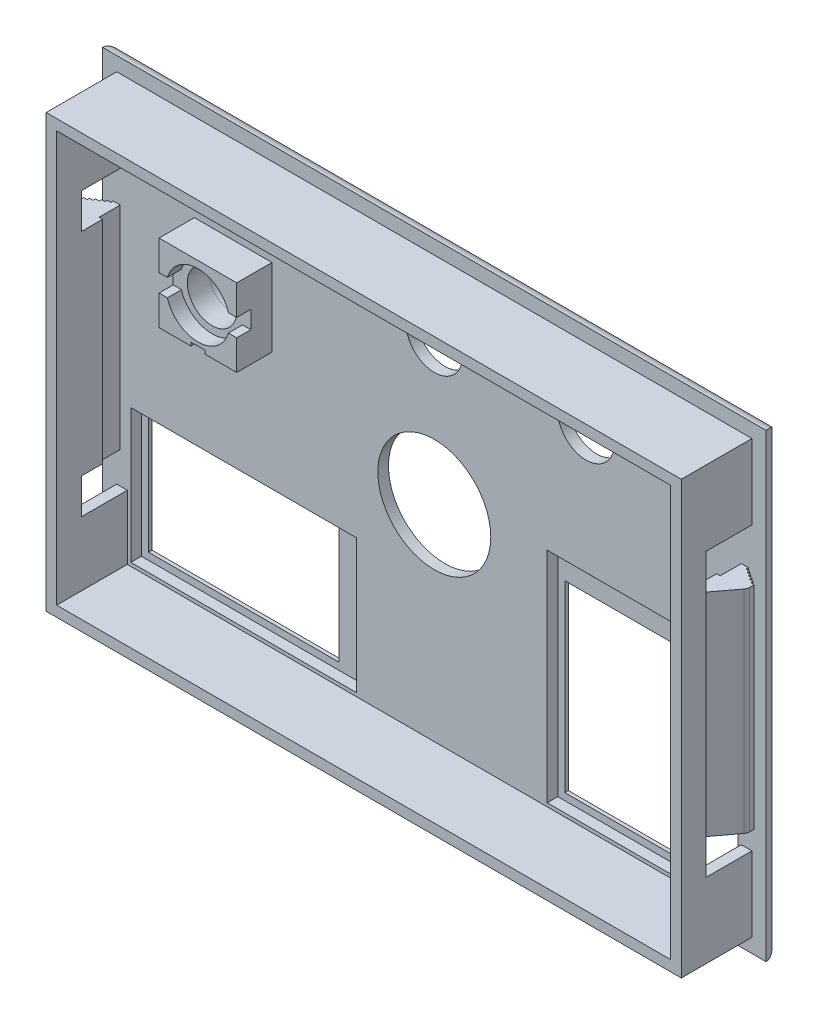
SolidWorks part; units mm, degrees
ref_plane "前视基准面" through (0, 0, 0) normal (0, 0, 1) x (1, 0, 0)
ref_plane "上视基准面" through (0, 0, 0) normal (0, 1, 0) x (1, 0, 0)
ref_plane "右视基准面" through (0, 0, 0) normal (1, 0, 0) x (0, 0, -1)
sketch "草图1" plane through (0, 0, 0) normal (0, 0, 1) x (1, 0, 0)
  line L1 (-47, 32.6) -> (47, 32.6)
  line L2 (-47, 32.6) -> (-47, -32.6)
  line L3 (-47, -32.6) -> (47, -32.6)
  line L4 (47, 32.6) -> (47, -32.6)
  line L5 (-47, 32.6) -> (47, -32.6) construction
  line L6 (-47, -32.6) -> (47, 32.6) construction
  point P0 (0, 0)
  dimension "D1" = 94
  dimension "D2" = 65.2
extrude "凸台-拉伸1" add sketch "草图1" along normal blind 2 contours L3 L4 L1 L2
sketch "草图2" plane through (0, 0, 2) normal (0, 0, 1) x (1, 0, 0)
  line L0 (-15, -27.6) -> (-42, -10.6) construction
  line L1 (-15, -27.6) -> (-42, -27.6)
  line L2 (-15, -27.6) -> (-15, -10.6)
  line L3 (-15, -10.6) -> (-42, -10.6)
  line L4 (-42, -27.6) -> (-42, -10.6)
  line L5 (42, -27.6) -> (17, -27.6)
  line L6 (42, -27.6) -> (42, -1.6)
  line L7 (42, -1.6) -> (17, -1.6)
  line L8 (17, -27.6) -> (17, -1.6)
  line L9 (-15, -10.6) -> (-42, -27.6) construction
  line L10 (42, -27.6) -> (17, -1.6) construction
  line L11 (42, -1.6) -> (17, -27.6) construction
  circle A0 centre (0, 0) radius 8
  circle A1 centre (-28.5, 12.7) radius 3.5
  circle A2 centre (37.5, 20.2) radius 4
  circle A3 centre (21.5, 20.2) radius 4
  circle A4 centre (0, 20.2) radius 4
  point P14 (-28.5, -19.1)
  point P24 (29.5, -14.6)
  dimension "D5" = 16
  dimension "D6" = 7
  dimension "D8" = 8
  dimension "D11" = 8
  dimension "D15" = 8
  dimension "D16" = 8
  dimension "D1" = 17
  dimension "D2" = 27
  dimension "D3" = 26
  dimension "D4" = 25
  dimension "D7" = 19.1
  dimension "D9" = 28.5
  dimension "D10" = 29.5
  dimension "D12" = 20.2
  dimension "D13" = 8
  dimension "D17" = 12.7
extrude "切除-拉伸1" cut sketch "草图2" against normal blind 2
sketch "草图3" plane through (0, 0, 2) normal (0, 0, 1) x (1, 0, 0)
  line L1 (43, -28.6) -> (-43, -28.6)
  line L2 (43, -28.6) -> (43, 28.6)
  line L3 (43, 28.6) -> (-43, 28.6)
  line L4 (-43, -28.6) -> (-43, 28.6)
  line L5 (45, -30.6) -> (-45, -30.6)
  line L6 (45, -30.6) -> (45, 30.6)
  line L7 (45, 30.6) -> (-45, 30.6)
  line L8 (-45, -30.6) -> (-45, 30.6)
  dimension "D1" = 2
  dimension "D2" = 2
  dimension "D3" = 2
  dimension "D4" = 2
  dimension "D5" = 43
  dimension "D6" = 28.6
  dimension "D7" = 28.6
  dimension "D8" = 43
extrude "凸台-拉伸2" add sketch "草图3" along normal blind 10 contours L6 L7 L8 L5 | L2 L3 L4 L1
sketch "草图4" plane through (0, 0, 0) normal (0, 0, -1) x (-1, 0, 0)
  circle A1 centre (0, 0) radius 9
  circle A2 centre (0, 20.2) radius 5
  circle A3 centre (-21.5, 20.2) radius 5
  circle A4 centre (-37.5, 20.2) radius 5
  dimension "D2" = 18
  dimension "D11" = 10
  dimension "D12" = 10
  dimension "D13" = 10
extrude "切除-拉伸4" cut sketch "草图4" against normal blind 0.5
sketch "草图5" plane through (0, 0, 2) normal (0, 0, 1) x (1, 0, 0)
  line L0 (17, -27.6) -> (42, -27.6) construction
  line L1 (43, -28.6) -> (16, -28.6)
  line L2 (43, -28.6) -> (43, 2.4)
  line L3 (43, 2.4) -> (16, 2.4)
  line L4 (16, -28.6) -> (16, 2.4)
  line L5 (42, -27.6) -> (42, -1.6) construction
  line L6 (17, -1.6) -> (17, -27.6) construction
  line L7 (42, -1.6) -> (17, -1.6) construction
  line L8 (-42, -27.6) -> (-15, -27.6) construction
  line L9 (-11, -28.6) -> (-43, -28.6)
  line L10 (-11, -28.6) -> (-11, -9.6)
  line L11 (-11, -9.6) -> (-43, -9.6)
  line L12 (-43, -28.6) -> (-43, -9.6)
  line L14 (-42, -10.6) -> (-42, -27.6) construction
  line L15 (-15, -10.6) -> (-42, -10.6) construction
  line L16 (-15, -27.6) -> (-15, -10.6) construction
  dimension "D1" = 1
  dimension "D2" = 1
  dimension "D3" = 1
  dimension "D4" = 4
  dimension "D5" = 1
  dimension "D6" = 1
  dimension "D7" = 1
  dimension "D8" = 4
extrude "切除-拉伸5" cut sketch "草图5" against normal blind 1.5
sketch "草图6" plane through (0, 0, 2) normal (0, 0, 1) x (1, 0, 0)
  line L0 (-28.5, 9.2) -> (-28.5, 16.2) construction
  line L6 (-22.5, 6.7) -> (-34.5, 6.7)
  line L7 (-22.5, 6.7) -> (-22.5, 18.7)
  line L8 (-22.5, 18.7) -> (-34.5, 18.7)
  line L9 (-34.5, 6.7) -> (-34.5, 18.7)
  line L10 (-22.5, 6.7) -> (-34.5, 18.7) construction
  line L11 (-22.5, 18.7) -> (-34.5, 6.7) construction
  circle A0 centre (-28.5, 12.7) radius 3.5 construction
  point P0 (-28.5, 12.7)
  circle M18 centre (-28.5, 12.7) radius 3.5
  dimension "D1" = 12
  dimension "D2" = 12
extrude "凸台-拉伸4" add sketch "草图6" along normal blind 5 separate body contours L9 L6 L7 L8 M18
sketch "草图7" plane through (0, 0, 7) normal (0, 0, 1) x (1, 0, 0)
  line L0 (-28.5, 9.2) -> (-28.5, 4.2907) construction
  line L1 (-22.5, 6.7) -> (-34.5, 6.7) construction
  line L2 (-27.5, 6.7) -> (-29.5, 6.7)
  line L3 (-27.5, 6.7) -> (-27.5, 7.7)
  line L4 (-27.5, 7.7) -> (-29.5, 7.7)
  line L5 (-29.5, 6.7) -> (-29.5, 7.7)
  circle A0 centre (-28.5, 12.7) radius 3.5 construction
  dimension "D1" = 2
  dimension "D3" = 1
extrude "切除-拉伸6" cut sketch "草图7" against normal blind 3
sketch "草图9" plane through (45, 0, 0) normal (1, 0, 0) x (0, 0, -1)
  line L0 (-8.5, 20) -> (-8.5, 15)
  line L1 (-8.5, 15) -> (-2.5, 15)
  line L2 (-2.5, 15) -> (-2.5, -15)
  line L3 (-2.5, -15) -> (-8.5, -15)
  line L4 (-8.5, -15) -> (-8.5, -20)
  line L5 (-8.5, -20) -> (-4.5187, -20)
  line L6 (-4.5187, -20) -> (-2, -20)
  line L7 (-2, -20) -> (-2, 20)
  line L8 (-2, 20) -> (-8.5, 20)
  line L9 (-2, -30.6) -> (-2, 30.6) construction
  line L10 (-20.086, 0) -> (-0.5045, 0) construction
  point P13 (-8.5, -17.5)
  point P14 (-8.5, 17.5)
  dimension "D1" = 30
  dimension "D2" = 40
  dimension "D4" = 0.5
  dimension "D5" = 6
  dimension "D6" = 6
extrude "切除-拉伸7" cut sketch "草图9" against normal up to next (2 mm away)
sketch "草图10" plane through (45, 0, 0) normal (1, 0, 0) x (0, 0, -1)
  line L1 (-8.5, 15) -> (-2.5, 15)
  line L2 (-8.5, 15) -> (-8.5, -15)
  line L3 (-8.5, -15) -> (-2.5, -15)
  line L4 (-2.5, 15) -> (-2.5, -15)
extrude "凸台-拉伸5" add sketch "草图10" along normal blind 3
sketch "草图13" plane through (0, 15, 0) normal (0, 1, 0) x (1, 0, 0)
  line L1 (48, -2.5) -> (48, -8.5) construction
  line L2 (48, -4.5) -> (48, -2.5)
  line L3 (43, -2.5) -> (48, -2.5) construction
  line L6 (48, -4.5) -> (47.5, -4.5)
  line L7 (47.5, -4.5) -> (47.5, -4.1693)
  line L8 (47.5, -4.1693) -> (47, -4.1693)
  line L9 (47, -4.1693) -> (47, -3.84)
  line L10 (47, -3.84) -> (46.5, -3.84)
  line L11 (46.5, -3.84) -> (46.5, -3.503)
  line L12 (46.5, -3.503) -> (46, -3.503)
  line L13 (46, -3.503) -> (46, -3.1684)
  line L14 (46, -3.1684) -> (45.5, -3.1684)
  line L15 (45.5, -3.1684) -> (45.5, -2.8377)
  line L16 (45.5, -2.8377) -> (45, -2.8377)
  line L17 (45, -2.8377) -> (45, -2.5)
  line L18 (48, -2.5) -> (45, -2.5)
  point P19 (47.25, -4.1693)
  dimension "D1" = 0.5
  dimension "D2" = 0.5
  dimension "D3" = 0.5
  dimension "D4" = 0.5
  dimension "D5" = 0.5
  dimension "D6" = 0.5
  dimension "D7" = 2
  dimension "D8" = 1.6693
  dimension "D9" = 1.34
  dimension "D10" = 1.003
  dimension "D11" = 0.6684
  dimension "D12" = 0.3377
extrude "切除-拉伸9" cut sketch "草图13" against normal up to next (30 mm away)
sketch "草图14" plane through (0, 15, 0) normal (0, 1, 0) x (1, 0, 0)
  line L0 (45, -8.5) -> (48, -4.5)
  line L1 (48, -4.5) -> (48, -8.5)
  line L2 (48, -8.5) -> (45, -8.5)
extrude "切除-拉伸10" cut sketch "草图14" against normal up to next (30 mm away)
sketch "草图15" plane through (0, 15, 0) normal (0, 1, 0) x (1, 0, 0)
  line L0 (47.5, -4.5) -> (47.5, -5.1667)
  line L1 (48, -4.5) -> (45, -8.5) construction
  line L2 (47.5, -5.1667) -> (48, -4.5)
  line L3 (48, -4.5) -> (47.5, -4.5)
extrude "切除-拉伸11" cut sketch "草图15" against normal up to next (30 mm away)
fillet "圆角1" radius 1 1 edges at (47.5, 0, 5.1667)
ref_plane "基准面1" through (0, 0, 0) normal (0, -1, 0) x (-1, 0, 0)
ref_plane "基准面2" through (0, 0, 0) normal (1, 0, 0) x (0, 0, -1)
fillet "圆角2" radius 2 4 edges at (47, 0, 0) (0, -32.6, 0) (-47, 0, 0) (0, 32.6, 0)
mirror "镜向9" about plane through (0, 0, 0) normal (1, 0, 0) of "凸台-拉伸5", "切除-拉伸9", "切除-拉伸11", "切除-拉伸10", "圆角1", "切除-拉伸7"
sketch "草图17" plane through (0, 0, 7) normal (0, 0, 1) x (1, 0, 0)
  circle A0 centre (-28.5, 12.7) radius 4.5
  circle A1 centre (-28.5, 12.7) radius 3.5 construction
  dimension "D1" = 9
extrude "切除-拉伸13" cut sketch "草图17" against normal blind 2
sketch "草图18" plane through (0, 0, 7) normal (0, 0, 1) x (1, 0, 0)
  line L0 (-34.5, 6.7) -> (-34.5, 18.7) construction
  line L1 (-34.5, 11.45) -> (-32.8229, 11.45)
  line L2 (-34.5, 11.45) -> (-34.5, 13.95)
  line L3 (-34.5, 13.95) -> (-32.8229, 13.95)
  line L4 (-32.8229, 11.45) -> (-32.8229, 13.95)
  line L5 (-22.5, 12.7) -> (-37.3749, 12.7) construction
  line L6 (-22.5, 6.7) -> (-22.5, 18.7) construction
  circle A0 centre (-28.5, 12.7) radius 4.5 construction
  dimension "D1" = 2.5
extrude "切除-拉伸14" cut sketch "草图18" against normal blind 2
ref_plane "基准面3" through (-28.5, 0, 0) normal (1, 0, 0) x (0, 0, -1)
mirror "镜向10" about plane through (-28.5, 0, 0) normal (1, 0, 0) of "切除-拉伸14"
sketch "草图19" plane through (0, 15, 0) normal (0, 1, 0) x (1, 0, 0)
  line L0 (43, -2.5) -> (45, -2.5) construction
  line L1 (43, -2.5) -> (44, -2.5)
  line L2 (43, -2.5) -> (43, -5.5)
  line L3 (43, -5.5) -> (44, -5.5)
  line L4 (44, -2.5) -> (44, -5.5)
  dimension "D1" = 1
  dimension "D2" = 3
extrude "切除-拉伸15" cut sketch "草图19" against normal up to next (30 mm away)
mirror "镜向11" about plane through (0, 0, 0) normal (1, 0, 0) of "切除-拉伸15"
sketch "草图21" plane through (0, 0, 12) normal (0, 0, 1) x (1, 0, 0)
  line L0 (43, -28.6) -> (43, 28.6) construction
  line L1 (43.5, -29.1) -> (-43.5, -29.1)
  line L2 (43.5, -29.1) -> (43.5, 29.1)
  line L3 (43.5, 29.1) -> (-43.5, 29.1)
  line L4 (-43.5, -29.1) -> (-43.5, 29.1)
  line L5 (43, -28.6) -> (-43, -28.6) construction
  line L6 (-43, 20) -> (-43, 28.6) construction
  line L7 (43, 28.6) -> (-43, 28.6) construction
  line L9 (43, -28.6) -> (-43, -28.6)
  line L10 (43, -28.6) -> (43, 28.6)
  line L11 (43, 28.6) -> (-43, 28.6)
  line L12 (-43, -28.6) -> (-43, 28.6)
  dimension "D1" = 0.5
  dimension "D2" = 0.5
  dimension "D3" = 0.5
  dimension "D4" = 0.5
extrude "切除-拉伸27" cut sketch "草图21" against normal blind 10
sketch "草图24" plane through (0, 0, 7) normal (0, 0, 1) x (1, 0, 0)
  line L0 (-22.5, 6.7) -> (-27.5, 6.7) construction
  line L1 (-23, 7.2) -> (-34, 7.2)
  line L2 (-23, 7.2) -> (-23, 18.2)
  line L3 (-23, 18.2) -> (-34, 18.2)
  line L4 (-34, 7.2) -> (-34, 18.2)
  line L5 (-22.5, 6.7) -> (-22.5, 11.45) construction
  line L6 (-34.5, 6.7) -> (-34.5, 11.45) construction
  line L7 (-22.5, 18.7) -> (-34.5, 18.7) construction
  line L9 (-22.5, 6.7) -> (-34.5, 6.7)
  line L10 (-22.5, 6.7) -> (-22.5, 18.7)
  line L11 (-22.5, 18.7) -> (-34.5, 18.7)
  line L12 (-34.5, 6.7) -> (-34.5, 18.7)
  dimension "D1" = 0.5
  dimension "D2" = 0.5
  dimension "D3" = 0.5
  dimension "D4" = 0.5
extrude "切除-拉伸28" cut sketch "草图24" against normal up to next contours L2 L3 L4 L1 | L10 L11 L12 L9
